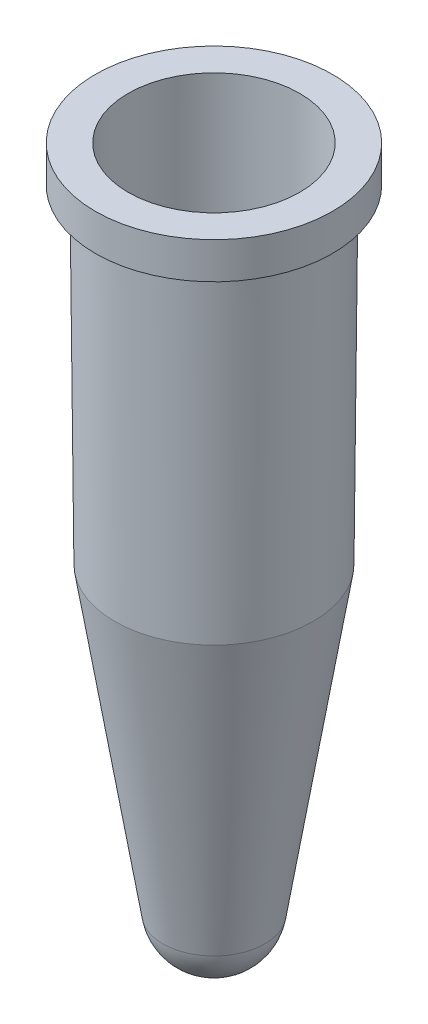
SolidWorks part; units mm, degrees
ref_plane "Front Plane" through (0, 0, 0) normal (0, 0, 1) x (1, 0, 0)
ref_plane "Top Plane" through (0, 0, 0) normal (0, 1, 0) x (1, 0, 0)
ref_plane "Right Plane" through (0, 0, 0) normal (1, 0, 0) x (0, 0, -1)
sketch "Sketch1" plane through (0, 0, 0) normal (0, 0, 1) x (1, 0, 0)
  line L0 (-4.7, 0) -> (-6.5, 0)
  line L1 (-6.5, 0) -> (-6.5, -2)
  line L2 (-6.5, -2) -> (-5.5826, -2)
  line L3 (-5.5826, -2) -> (-5.4255, -20)
  line L4 (-5.4255, -20) -> (-2.7942, -36.6136)
  line L5 (0, 0) -> (0, -78.5552) construction
  line L6 (-4.6826, -1.9921) -> (-4.5261, -19.9253)
  line L7 (-4.5261, -19.9253) -> (-1.9052, -36.4728)
  line L8 (-4.6826, -1.9921) -> (-4.7, 0)
  line L10 (4.6826, -1.9921) -> (4.7, 0)
  line L11 (4.7, 0) -> (6.5, 0)
  line L12 (6.5, -2) -> (5.5826, -2)
  line L13 (5.5826, -2) -> (5.4255, -20)
  line L14 (4.6826, -1.9921) -> (4.5261, -19.9253)
  line L15 (4.5261, -19.9253) -> (1.9052, -36.4728)
  line L16 (5.4255, -20) -> (2.7942, -36.6136)
  line L17 (5.5826, -2) -> (5.5826, -11.7732) construction
  line L18 (22, 17.9555) -> (22, -54.2112) construction
  line L19 (6.5, -2) -> (18, -2)
  line L20 (18, -2) -> (18, 2)
  line L21 (18, 2) -> (26, 2)
  line L22 (26.569, 3) -> (17.431, 3)
  line L23 (17.431, 3) -> (17.3, 0)
  line L24 (17.3, 0) -> (15.5, 0)
  line L26 (14, -1.5) -> (8, -1.5)
  line L27 (17.3, 0) -> (17.3, 13.958) construction
  line L28 (26.569, 3) -> (26.7, 0)
  line L29 (26, -2) -> (26, 2)
  line L31 (26.7, 0) -> (28.5, 0)
  line L33 (26, -2) -> (28.5, -2)
  line L34 (28.5, 0) -> (28.5, -2)
  line L35 (0, -38.1) -> (0, -39)
  line L36 (5.5826, -2) -> (5.5826, 0)
  line L37 (17.3, 0) -> (17.3, -2)
  line L38 (15.5, 0) -> (6.5, 0)
  line L39 (8, -1.5) -> (9.3403, -2.8403) construction
  line L40 (22, 2) -> (22, 3)
  line L41 (6.5, 0) -> (6.5, -2)
  arc A0 (-2.7942, -36.6136) -> (2.7942, -36.6136) centre (0, -36.171) ccw
  arc A1 (-1.9052, -36.4728) -> (1.9052, -36.4728) centre (0, -36.171) ccw
  arc A2 (-2.7942, -36.6136) -> (-0.2074, -38.9924) centre (0, -36.171) ccw construction
  arc A4 (-1.9052, -36.4728) -> (-0.1414, -38.0948) centre (0, -36.171) ccw construction
  arc A6 (6.5, 0) -> (8, -1.5) centre (8, 0) ccw
  arc A7 (15.5, 0) -> (14, -1.5) centre (14, 0) cw
  point P25 (0, -39)
  point P44 (22, 3)
  point P46 (22, 2)
  dimension "D9" = 22
  dimension "D17" = 45
  dimension "D18" = 1.5
  dimension "D16" = 13
  dimension "D1" = 0.9
  dimension "D2" = 2
  dimension "D3" = 20
  dimension "D4" = 9.4
  dimension "D5" = 13
  dimension "D6" = 39
  dimension "D7" = 0.5
  dimension "D8" = 9
  dimension "D10" = 4
  dimension "D11" = 5
  dimension "D12" = 2.5
  dimension "D13" = 0.5
  dimension "D14" = 9.4
  dimension "D15" = 8
revolve "Revolve25" add sketch "Sketch1" angle 360 about L5 region at (-5.0867, -0.9995, 0)
revolve "Revolve31" add sketch "Sketch1<10>" angle 360 about L18 region at (22.082, 2.5, 0)
sketch "Sketch1<10>" plane through (0, 0, 0) normal (0, 0, 1) x (1, 0, 0) same geometry as "Sketch1"
ref_plane "Plane1" through (0, -2, 0) normal (0, -1, 0) x (-1, 0, 0)
sketch "Sketch2" plane through (0, -2, 0) normal (0, -1, 0) x (-1, 0, 0)
  line L0 (-22, 6.5) -> (-22, 4)
  line L1 (-22, -6.5) -> (-22, -4)
  line L3 (-14.8455, 1.25) -> (-7.1545, 1.25)
  line L5 (-14.8455, -1.25) -> (-7.1545, -1.25)
  line L8 (-7.1545, 1.25) -> (-7.1545, -1.25)
  line L9 (-14.8455, -1.25) -> (-14.8455, 1.25)
  line L10 (-15.7994, -1.95) -> (-15.7994, 1.95)
  line L11 (-6.2006, 1.95) -> (-6.2006, -1.95)
  circle A0 centre (-22, 0) radius 6.5 construction
  circle A1 centre (-22, 0) radius 4 construction
  arc A2 (-22, -4) -> (-22, 4) centre (-22, 0) cw
  arc A3 (-22, 6.5) -> (-15.7994, 1.95) centre (-22, 0) cw
  arc A4 (-14.8455, 1.25) -> (-15.7994, 1.95) centre (-14.8455, 2.25) cw
  arc A5 (-22, -6.5) -> (-15.7994, -1.95) centre (-22, 0) ccw
  arc A6 (-14.8455, -1.25) -> (-15.7994, -1.95) centre (-14.8455, -2.25) ccw
  arc A7 (0, 6.5) -> (-6.2006, 1.95) centre (0, 0) ccw
  circle A8 centre (0, 0) radius 6.5 construction
  arc A9 (-6.2006, 1.95) -> (-7.1545, 1.25) centre (-7.1545, 2.25) cw
  arc A10 (0, -6.5) -> (-6.2006, -1.95) centre (0, 0) cw
  arc A11 (-7.1545, -1.25) -> (-6.2006, -1.95) centre (-7.1545, -2.25) cw
  ellipse E0 centre (-22, 0) end of major axis (-13.5, 0) minor radius 6.5
  point P1 (-22, 6.5)
  point P7 (-22, -6.5)
  dimension "D2" = 1
  dimension "D3" = 1
  dimension "D4" = 6.5
  dimension "D7" = 2.5
  dimension "D5" = 1
  dimension "D6" = 1
  dimension "D1" = 8.5
extrude "Boss-Extrude4" add sketch "Sketch2" against normal up to surface (2 mm away) contours L0 E0 L1 A2 region at (26.3861, -2, 0) up to face at (15.5, 0, 0)
delete or keep bodies "Body-Delete/Keep 1" type delete bodies bodies 106
scale "Scale1" scale about centroid uniform scaling yes scale factor 0.510873
